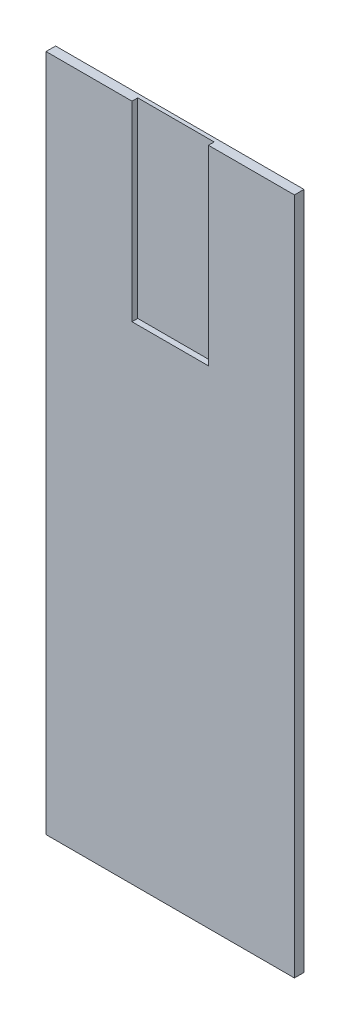
SolidWorks part; units mm, degrees
ref_plane "Front Plane" through (0, 0, 0) normal (0, 0, 1) x (1, 0, 0)
ref_plane "Top Plane" through (0, 0, 0) normal (0, 1, 0) x (1, 0, 0)
ref_plane "Right Plane" through (0, 0, 0) normal (1, 0, 0) x (0, 0, -1)
sketch "Sketch1" plane through (0, 0, 0) normal (0, 0, 1) x (1, 0, 0)
  line L1 (0, 0) -> (330.2, 0)
  line L2 (0, 0) -> (0, 901.7)
  line L3 (0, 901.7) -> (330.2, 901.7)
  line L4 (330.2, 0) -> (330.2, 901.7)
  dimension "D1" = 901.7
  dimension "D2" = 330.2
extrude "Boss-Extrude1" add sketch "Sketch1" along normal blind 12.7
sketch "Sketch2" plane through (0, 0, 12.7) normal (0, 0, 1) x (1, 0, 0)
  line L0 (330.2, 901.7) -> (0, 901.7) construction
  line L1 (114.3, 901.7) -> (215.9, 901.7)
  line L2 (114.3, 901.7) -> (114.3, 647.7)
  line L3 (114.3, 647.7) -> (215.9, 647.7)
  line L4 (215.9, 901.7) -> (215.9, 647.7)
  point P4 (165.1, 901.7)
  point P7 (165.1, 901.7)
  dimension "D1" = 101.6
  dimension "D2" = 254
extrude "Cut-Extrude1" cut sketch "Sketch2" against normal blind 7.62
